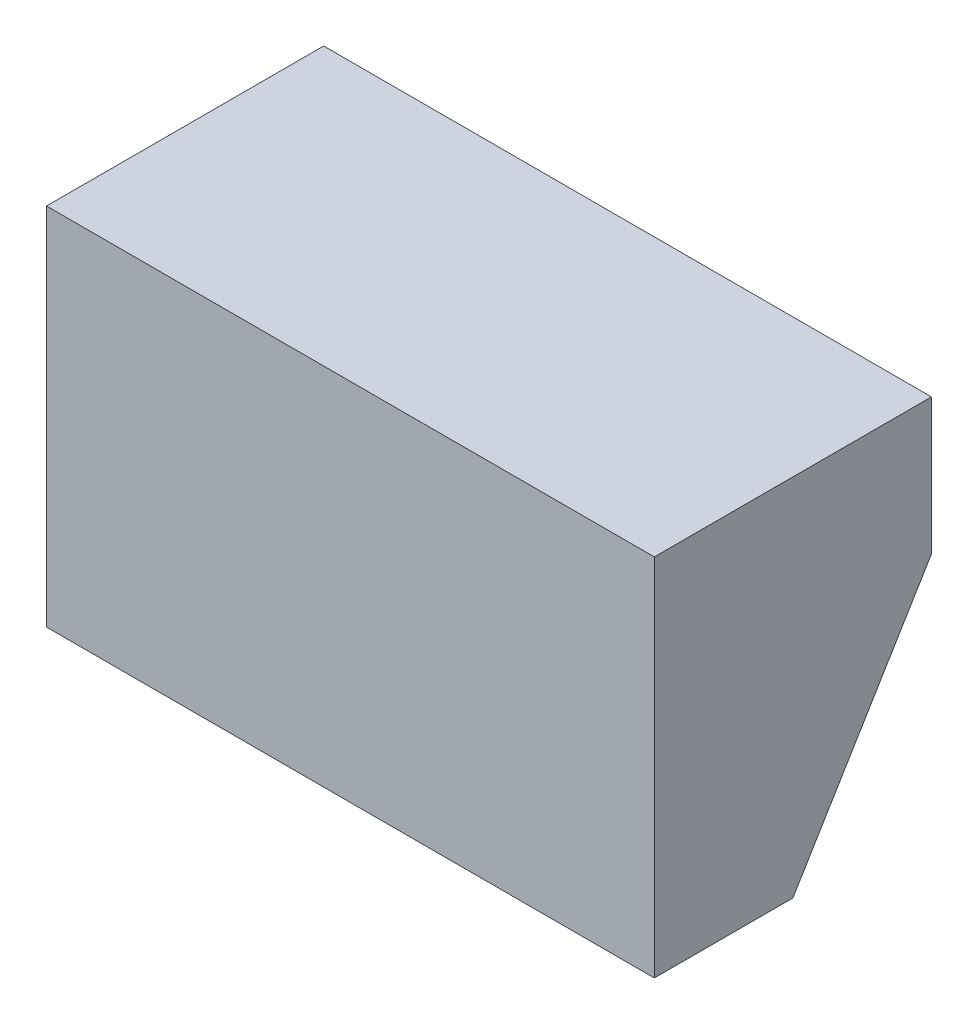
SolidWorks part; units mm, degrees
material "ABS PC"
ref_plane "前视基准面" through (0, 0, 0) normal (0, 0, 1) x (1, 0, 0)
ref_plane "上视基准面" through (0, 0, 0) normal (0, 1, 0) x (1, 0, 0)
ref_plane "右视基准面" through (0, 0, 0) normal (1, 0, 0) x (0, 0, -1)
sketch "Sketch1" plane through (0, 0, 0) normal (0, 0, 1) x (1, 0, 0)
  line L1 (-125, -75) -> (125, -75)
  line L2 (-125, -75) -> (-125, 75)
  line L3 (-125, 75) -> (125, 75)
  line L4 (125, -75) -> (125, 75)
  line L5 (-125, -75) -> (125, 75) construction
  line L6 (-125, 75) -> (125, -75) construction
  point P0 (0, 0)
  dimension "D1" = 250
  dimension "D2" = 150
extrude "Boss-Extrude1" add sketch "Sketch1" along normal blind 114
sketch "sketchCenterLine" plane through (0, 0, 114) normal (0, 0, 1) x (1, 0, 0)
  line L0 (0, 0) -> (-160.1488, 0) construction
  line L1 (-170, 12.5) -> (-115, 12.5)
  line L2 (-97.3223, 19.8223) -> (-69.467, 47.6777)
  line L3 (-51.7893, 55) -> (70, 55)
  line L4 (95, 30) -> (95, -30)
  line L5 (70, -55) -> (-51.7893, -55)
  line L6 (-69.467, -47.6777) -> (-97.3223, -19.8223)
  line L7 (-115, -12.5) -> (-170, -12.5)
  line L8 (-125, 75) -> (-125, -75) construction
  arc A0 (70, -55) -> (95, -30) centre (70, -30) ccw
  arc A1 (95, 30) -> (70, 55) centre (70, 30) ccw
  arc A2 (-115, 12.5) -> (-97.3223, 19.8223) centre (-115, 37.5) ccw
  arc A3 (-97.3223, -19.8223) -> (-115, -12.5) centre (-115, -37.5) ccw
  arc A4 (-51.7893, -55) -> (-69.467, -47.6777) centre (-51.7893, -30) cw
  arc A5 (-69.467, 47.6777) -> (-51.7893, 55) centre (-51.7893, 30) cw
  point P24 (-62.1447, -55)
  point P27 (-62.1447, 55)
  dimension "D1" = 25
  dimension "D2" = 25
  dimension "D8" = 10
  dimension "D3" = 95
  dimension "D4" = 110
  dimension "D5" = 25
  dimension "D6" = 45
  dimension "D7" = 45
sketch3d "3DSketch1"
  line L0 (125, -75, 114) -> (125, -75, 0) construction
  line L1 (125, -75, 0) -> (125, 75, 0) construction
  line L2 (-125, -75, 0) -> (125, -75, 0) construction
  point P0 (125, -75, 57)
  point P1 (125, 19.0618, 0)
  point P4 (42.2925, -75, 0)
ref_plane "Plane1" through (27.9069, -24.5383, -40.4932) normal (-0.5078, 0.4465, 0.7368) x (0.8615, 0.2632, 0.4343)
sketch "Sketch4" plane through (27.9069, -24.5383, -40.4932) normal (-0.5078, 0.4465, 0.7368) x (0.8615, 0.2632, 0.4343)
  line L1 (-16.3307, -143.8321) -> (142.4953, -143.8321)
  line L2 (-16.3307, -143.8321) -> (-16.3307, 25.2667)
  line L3 (-16.3307, 25.2667) -> (142.4953, 25.2667)
  line L4 (142.4953, -143.8321) -> (142.4953, 25.2667)
extrude "Cut-Extrude1" cut sketch "Sketch4" against normal blind 114
